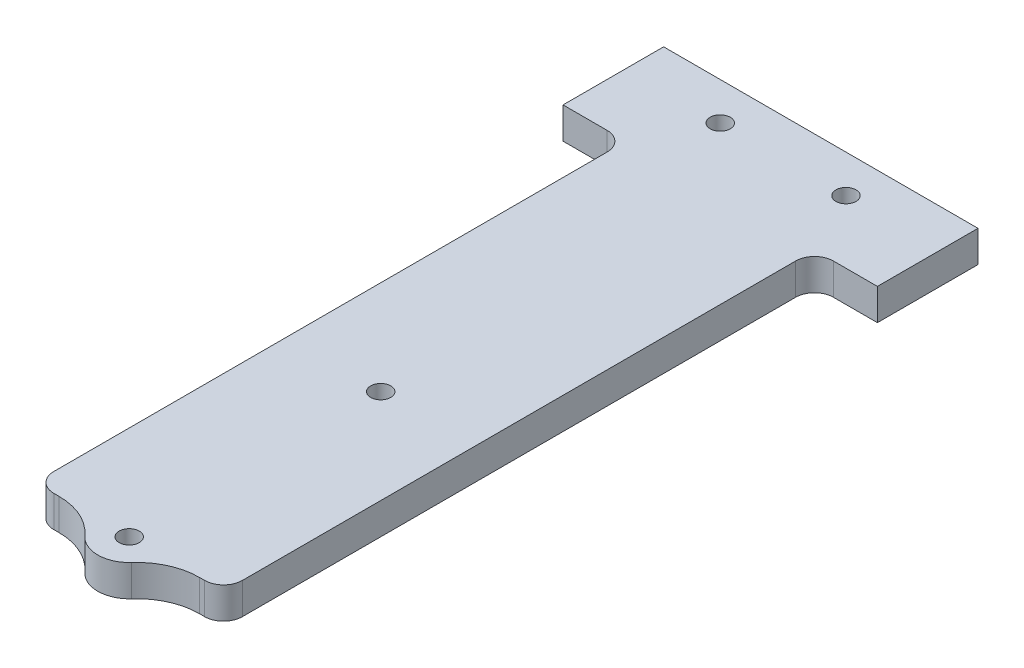
SolidWorks part; units mm, degrees
ref_plane "Front Plane" through (0, 0, 0) normal (0, 0, 1) x (1, 0, 0)
ref_plane "Top Plane" through (0, 0, 0) normal (0, 1, 0) x (1, 0, 0)
ref_plane "Right Plane" through (0, 0, 0) normal (1, 0, 0) x (0, 0, -1)
sketch "Sketch1" plane through (0, 0, 0) normal (0, 1, 0) x (1, 0, 0)
  line L1 (0, 0) -> (30, 0)
  line L2 (0, 0) -> (0, 110)
  line L3 (0, 110) -> (30, 110)
  line L4 (30, 0) -> (30, 110)
  dimension "D1" = 110
  dimension "D2" = 30
extrude "Boss-Extrude1" add sketch "Sketch1" along normal blind 5
sketch "Sketch2" plane through (0, 5, 0) normal (0, 1, 0) x (1, 0, 0)
  line L0 (0, 0) -> (30, 0) construction
  circle A0 centre (15, 0) radius 5
  dimension "D1" = 10
extrude "Boss-Extrude2" add sketch "Sketch2" along normal blind 30 and the other way up to surface contours A0 other way up to face at (15, 0, -55)
sketch "Sketch6" plane through (0, 5, 0) normal (0, 1, 0) x (1, 0, 0)
  line L0 (15, 110) -> (15, 104) construction
  line L1 (-10, 110) -> (40, 110)
  line L2 (-10, 110) -> (-10, 104)
  line L3 (-10, 104) -> (40, 104)
  line L4 (40, 110) -> (40, 104)
  line L5 (30, 110) -> (0, 110) construction
  line L6 (0, 110) -> (0, 0) construction
  dimension "D1" = 10
  dimension "D2" = 6
extrude "Boss-Extrude5" add sketch "Sketch6" along normal up to surface and the other way up to surface up to face at (15, 35, 5) other way up to face at (15, 0, -35.8333)
sketch "Sketch3" plane through (0, 5, 0) normal (0, 1, 0) x (1, 0, 0)
  line L0 (15, 0) -> (15, 50)
  line L1 (0, 50) -> (30, 50)
  line L2 (30, 50) -> (15, 0)
  line L3 (0, 50) -> (15, 0)
  line L4 (0, 104) -> (0, 0) construction
  line L5 (30, 30) -> (0, 30)
  line L6 (30, 0) -> (30, 104) construction
  line L8 (0, 50) -> (30, 50)
  line L9 (0, 50) -> (0, 110)
  line L10 (0, 110) -> (30, 110)
  line L11 (30, 50) -> (30, 110)
  dimension "D1" = 50
  dimension "D2" = 30
  dimension "D3" = 20
extrude "Boss-Extrude6" add sketch "Sketch3" along normal up to surface (30 mm away) contours L5 L2 L1 L0 | L5 L0 L1 L3 up to face at (15, 35, 5)
sketch "Sketch7" plane through (0, 0, -104) normal (0, 0, 1) x (1, 0, 0)
  line L0 (-10, 0) -> (0, 0) construction
  line L1 (-10, 0) -> (40, 0)
  line L2 (-10, 0) -> (-10, 5)
  line L3 (-10, 5) -> (40, 5)
  line L4 (40, 0) -> (40, 5)
  line L5 (0, 5) -> (10, 5) construction
  line L6 (-10, 35) -> (-10, 0) construction
  line L7 (40, 35) -> (40, 0) construction
extrude "Boss-Extrude7" add sketch "Sketch7" along normal blind 10
sketch "Sketch8" plane through (0, 0, -104) normal (0, 0, 1) x (1, 0, 0)
  line L0 (-10, 25) -> (40, 25)
  line L1 (-10, 35) -> (-10, 5) construction
  line L2 (40, 35) -> (40, 5) construction
  line L3 (-10, 35) -> (40, 35) construction
  circle A0 centre (-5, 25) radius 1.6
  circle A1 centre (35, 25) radius 1.6
  point P10 (-4.698, 30.0488)
  point P11 (-4.4641, 28.8795)
  dimension "D4" = 3.2
  dimension "D1" = 10
  dimension "D2" = 5
  dimension "D3" = 5
extrude "Cut-Extrude1" cut sketch "Sketch8" against normal through all contours L0 A0 | L0 A0 | L0 A1 | L0 A1
sketch "Sketch9" plane through (0, 5, 0) normal (0, 1, 0) x (1, 0, 0)
  line L0 (-10, 104) -> (40, 104) construction
  line L1 (0, 94) -> (30, 94)
  line L2 (0, 94) -> (0, 104)
  line L3 (0, 104) -> (30, 104)
  line L4 (30, 94) -> (30, 104)
  line L5 (0, 50) -> (30, 50) construction
  line L6 (12.5, 94) -> (17.5, 94)
  line L7 (12.5, 94) -> (12.5, 50)
  line L8 (12.5, 50) -> (17.5, 50)
  line L9 (17.5, 94) -> (17.5, 50)
  line L10 (30, 50) -> (30, 94) construction
  line L11 (15, 94) -> (15, 50) construction
  line M10 (40, 104) -> (-10, 104)
  line M14 (0, 50) -> (30, 50)
  dimension "D1" = 5
extrude "Boss-Extrude8" add sketch "Sketch9" along normal up to surface (30 mm away) contours L1 L6 L4 L2 M10 | L11 L1 L7 M14 | L6 L11 L8 L9 up to face at (15, 35, -40)
sketch "Sketch10" plane through (0, 35, 0) normal (0, 1, 0) x (1, 0, 0)
  line L0 (0, 104) -> (30, 104) construction
  line L1 (15, 104) -> (15, 0) construction
  line L2 (24, 30) -> (6, 30) construction
  circle A0 centre (15, 0) radius 1.6
  circle A1 centre (15, 40) radius 1.6
  circle A2 centre (5, 104) radius 1.6
  circle A3 centre (25, 104) radius 1.6
  point P14 (15, 39.5394)
  point P15 (24.1636, 104)
  point P16 (6.102, 104)
  dimension "D1" = 3.2
  dimension "D2" = 20
  dimension "D3" = 10
  dimension "D4" = 10
extrude "Cut-Extrude2" cut sketch "Sketch10" against normal through all
fillet "Fillet3" radius 2 1 edges at (15, 5, -5)
fillet "Fillet4" radius 10 2 edges at (20, 3.5, 0) (10, 3.5, 0)
fillet "Fillet5" radius 3 9 edges at (27, 5, -40) (24, 20, -30) (6, 20, -30) (3, 5, -40) (30, 2.5, -94) (0, 2.5, -94) (0, 2.5, 0) (30, 2.5, 0) (15, 5, -30)
fillet "Fillet6" radius 2 2 edges at (30, 20, -94) (0, 20, -94)
sketch "Sketch12" plane through (17.5, 0, 0) normal (1, 0, 0) x (0, 0, -1)
  line L0 (-5, 35) -> (-5, 0) construction
  line L1 (110, 5) -> (-5, 5)
  line L2 (110, 5) -> (110, 35)
  line L3 (110, 35) -> (-5, 35)
  line L4 (-5, 5) -> (-5, 35)
  line L5 (3, 5) -> (39.5597, 5) construction
  line L6 (110, 35) -> (110, 0) construction
  line L7 (50, 35) -> (32.138, 35) construction
extrude "Cut-Extrude3" cut sketch "Sketch12" against normal through all both and the other way through all
sketch "Sketch14" plane through (0, 5, 0) normal (0, 1, 0) x (1, 0, 0)
  line L0 (40, 94) -> (33, 94) construction
  line L1 (-10, 94) -> (0, 94)
  line L2 (-10, 94) -> (-10, 102)
  line L3 (-10, 102) -> (0, 102)
  line L4 (0, 94) -> (0, 102)
  line L5 (40, 94) -> (30, 94)
  line L6 (40, 94) -> (40, 102)
  line L7 (40, 102) -> (30, 102)
  line L8 (30, 94) -> (30, 102)
  line L9 (40, 94) -> (40, 110) construction
  line L10 (0, 91) -> (0, 3) construction
  line L11 (30, 3) -> (30, 91) construction
  dimension "D1" = 8
extrude "Boss-Extrude9" [suppressed] add sketch "Sketch14" along normal blind 30
fillet "Fillet7" [suppressed] radius 2
sketch "Sketch15" plane through (0, 0, -94) normal (0, 0, 1) x (1, 0, 0)
  line L0 (-10, 15) -> (40, 15) construction
  line L1 (-10, 5) -> (-10, 0) construction
  line L2 (40, 0) -> (40, 5) construction
  line L3 (11.2732, 5) -> (3.8197, 5) construction
  circle A0 centre (-5, 15) radius 1.6
  circle A1 centre (35, 15) radius 1.6
  point P10 (-5.3045, 11.8837)
  point P11 (35.5352, 11.8837)
  dimension "D1" = 3.2
  dimension "D2" = 5
  dimension "D3" = 5
  dimension "D4" = 10
extrude "Cut-Extrude4" [suppressed] cut sketch "Sketch15" against normal through all both and the other way through all
